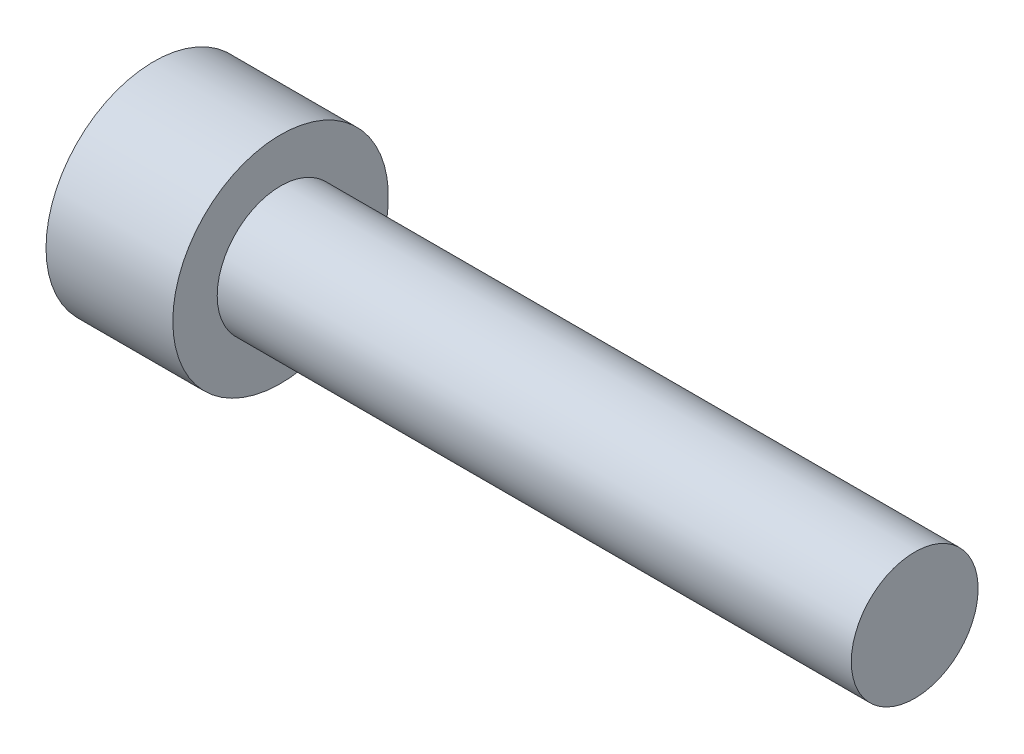
SolidWorks part; units mm, degrees
ref_plane "Front Plane" through (0, 0, 0) normal (0, 0, 1) x (1, 0, 0)
ref_plane "Top Plane" through (0, 0, 0) normal (0, 1, 0) x (1, 0, 0)
ref_plane "Right Plane" through (0, 0, 0) normal (1, 0, 0) x (0, 0, -1)
sketch "Screw Sketch" plane through (0, 0, 0) normal (0, 0, 1) x (1, 0, 0)
  line L0 (-1000, 0) -> (1000, 0) construction
  line L1 (-5, 0) -> (-5, 4.25)
  line L2 (-5, 4.25) -> (0, 4.25)
  line L3 (0, 4.25) -> (0, 2.5)
  line L4 (0, 2.5) -> (25, 2.5)
  line L5 (25, 2.5) -> (25, 0)
  line L6 (25, 0) -> (-5, 0)
revolve "Screw" add sketch "Screw Sketch" angle 360 about L0
ref_axis "Engine Axis" through (26.5, 0, 0) along (-1, 0, 0)
ref_plane "Head Top" through (-5, 0, 0) normal (1, 0, 0) x (0, 0, -1)
sketch "Socket Sketch" plane through (-5, 0, 0) normal (1, 0, 0) x (0, 0, -1)
  line L0 (2.3094, 0) -> (1.1547, 2)
  line L1 (1.1547, 2) -> (-1.1547, 2)
  line L2 (-1.1547, 2) -> (-2.3094, 0)
  line L3 (-2.3094, 0) -> (-1.1547, -2)
  line L4 (-1.1547, -2) -> (1.1547, -2)
  line L5 (1.1547, -2) -> (2.3094, 0)
extrude "Socket" cut sketch "Socket Sketch" along normal blind 2.5
